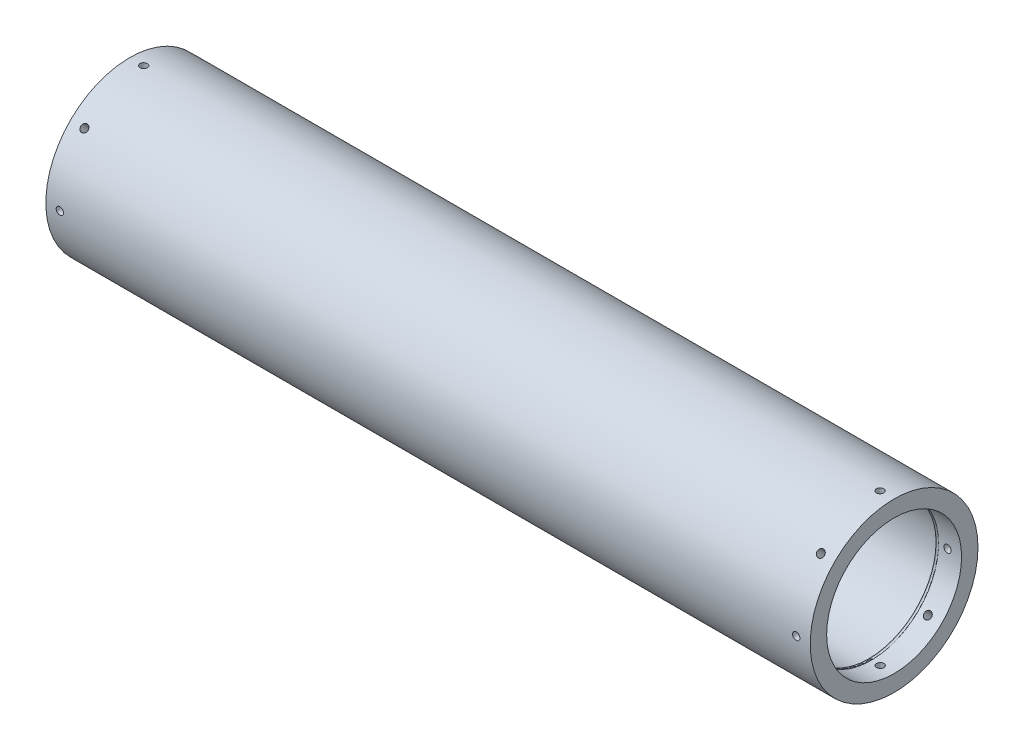
SolidWorks part; units mm, degrees
material "7075-T6 (SN)"
ref_plane "Front Plane" through (0, 0, 0) normal (0, 0, 1) x (1, 0, 0)
ref_plane "Top Plane" through (0, 0, 0) normal (0, 1, 0) x (1, 0, 0)
ref_plane "Right Plane" through (0, 0, 0) normal (1, 0, 0) x (0, 0, -1)
sketch "Sketch1" plane through (0, 0, 0) normal (1, 0, 0) x (0, 0, -1)
  circle A0 centre (0, 0) radius 45.9486
  circle A1 centre (0, 0) radius 57.15
  dimension "D1" = 91.8972
  dimension "D2" = 114.3
extrude "Boss-Extrude1" add sketch "Sketch1" along normal blind 520.7
sketch "Sketch2" plane through (0, 0, 0) normal (-1, 0, 0) x (0, 0, 1)
  circle A0 centre (0, 0) radius 44.5262
  circle A1 centre (0, 0) radius 45.9486
  dimension "D1" = 89.0524
extrude "Boss-Extrude2" add sketch "Sketch2" against normal blind 95.25
sketch "Sketch3" plane through (0, 0, 0) normal (0, 0, 1) x (1, 0, 0)
  line L0 (0, 44.5262) -> (0, -44.5262) construction
  line L1 (0, 0) -> (74.5933, 0) construction
  circle A0 centre (16.51, 44.323) radius 0.889
  dimension "D1" = 1.778
  dimension "D2" = 16.51
  dimension "D3" = 44.323
revolve "Cut-Revolve1" cut sketch "Sketch3" angle 360 about L1
ref_plane "Plane1" through (0, 0, 57.15) normal (0, 0, 1) x (1, 0, 0)
sketch "Sketch4" plane through (0, 0, 57.15) normal (0, 0, 1) x (1, 0, 0)
  circle A0 centre (9.525, 0) radius 2.4892
  dimension "D2" = 4.9784
  dimension "D1" = 9.525
extrude "Cut-Extrude1" cut sketch "Sketch4" against normal blind 19.05
pattern_circular "CirPattern1" count 8 every 45 about axis through (520.7, 0, 0) along (-1, 0, 0) of "Cut-Extrude1" reverse direction yes
sketch "Sketch5" plane through (0, 0, 57.15) normal (0, 0, 1) x (1, 0, 0)
  line L0 (520.7, -57.15) -> (520.7, 57.15) construction
  circle A0 centre (511.175, 0) radius 2.4892
  dimension "D2" = 4.9784
  dimension "D1" = 9.525
extrude "Cut-Extrude2" cut sketch "Sketch5" against normal blind 19.05
pattern_circular "CirPattern2" count 8 every 45 about axis through (520.7, 0, 0) along (-1, 0, 0) of "Cut-Extrude2"
sketch "Sketch6" plane through (0, 0, 0) normal (0, 0, 1) x (1, 0, 0)
  line L0 (520.7, -57.15) -> (520.7, 57.15) construction
  line L1 (0, 0) -> (569.0333, 0) construction
  circle A0 centre (504.19, 45.72) radius 0.889
  dimension "D2" = 1.778
  dimension "D3" = 16.51
  dimension "D1" = 45.72
revolve "Cut-Revolve2" cut sketch "Sketch6" angle 360 about L1
